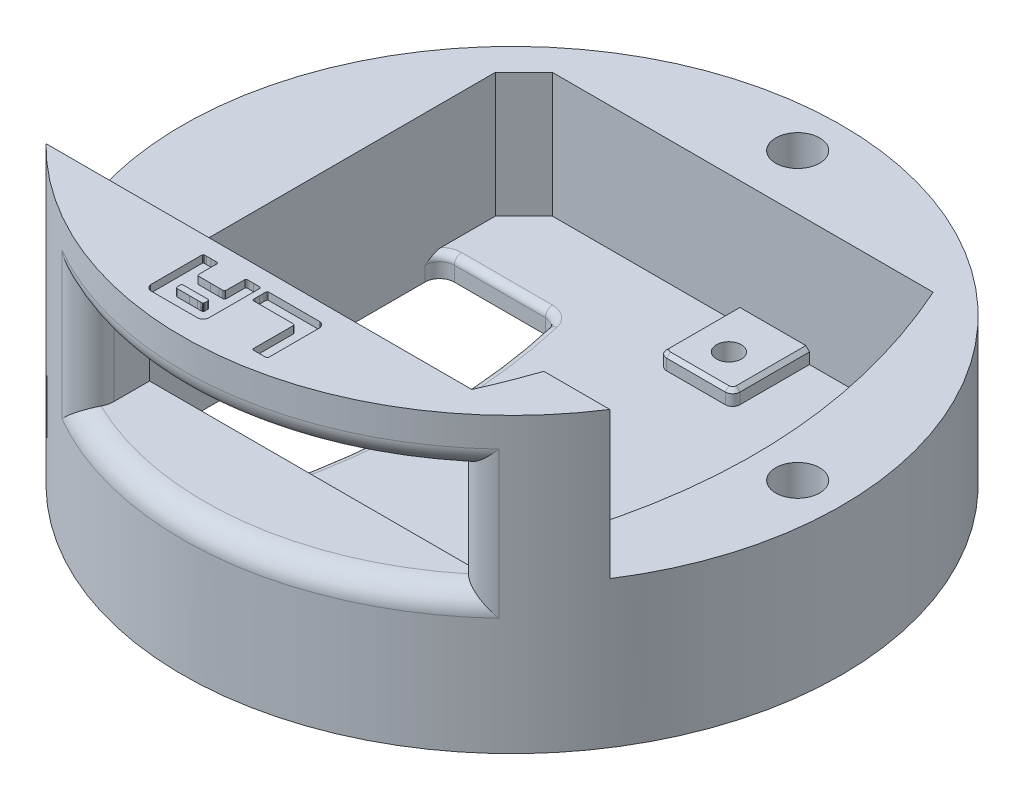
SolidWorks part; units mm, degrees
ref_plane "Plan de face" through (0, 0, 0) normal (0, 0, 1) x (1, 0, 0)
ref_plane "Plan de dessus" through (0, 0, 0) normal (0, 1, 0) x (1, 0, 0)
ref_plane "Plan de droite" through (0, 0, 0) normal (1, 0, 0) x (0, 0, -1)
sketch "Esquisse1" plane through (0, 0, 0) normal (0, 1, 0) x (1, 0, 0)
  circle A0 centre (0, 0) radius 45
  dimension "D1" = 90
extrude "Boss.-Extru.1" add sketch "Esquisse1" along normal blind 40
sketch "Esquisse2" plane through (0, 40, 0) normal (0, 1, 0) x (1, 0, 0)
  line L0 (-26, 31.5) -> (26, 31.5)
  line L1 (26, 0) -> (33, 0) construction
  line L2 (26, 31.5) -> (26, -31.5) construction
  line L3 (-26, 31.5) -> (-29.8891, 27.6109)
  line L4 (-29.8891, 27.6109) -> (-29.8891, 21.6109)
  line L5 (-29.8891, 21.6109) -> (-39.4711, 21.6109)
  line L6 (26, 0) -> (-63.3285, 0) construction
  line L7 (26, 31.5) -> (32.1364, 31.5) construction
  line L8 (-26, 31.5) -> (-32.1364, 31.5) construction
  line L9 (-29.8891, -21.6109) -> (-39.4711, -21.6109)
  line L10 (-29.8891, -27.6109) -> (-29.8891, -21.6109)
  line L11 (-26, -31.5) -> (-29.8891, -27.6109)
  line L12 (-26, -31.5) -> (26, -31.5)
  circle A0 centre (0, 0) radius 45 construction
  arc A1 (-39.4711, -21.6109) -> (-39.4711, 21.6109) centre (0, 0) cw
  spline S0 degree 2 poles (26, 31.5) (40, 0) (26, -31.5) knots 0 0 0 1 1 1
  circle M11 centre (0, 0) radius 45
  dimension "D1" = 52
  dimension "D2" = 7
  dimension "D3" = 63
  dimension "D4" = 135
  dimension "D5" = 5.5
  dimension "D6" = 6
extrude "Enlèv. mat.-Extru.1" cut sketch "Esquisse2" against normal offset from surface (37 mm away) 3 contours S0 L0 L3 L4 L5 L9 L10 L11 L12 M11 region at (-4.3513, 40, 0) up to face at (0, 0, 45)
sketch "Esquisse7" plane through (0, 3, 0) normal (0, 1, 0) x (1, 0, 0)
  line L0 (9.1109, 30) -> (-0.8891, 21) construction
  line L1 (9.1109, 30) -> (9.1109, 22)
  line L2 (8.1109, 21) -> (0.1109, 21)
  line L3 (-0.8891, 30) -> (-0.8891, 22)
  line L4 (-0.8891, 30) -> (9.1109, 30) construction
  line L5 (-0.8891, 30) -> (-0.8891, 31.5)
  line L6 (-0.8891, 31.5) -> (9.1109, 31.5)
  line L7 (9.1109, 30) -> (9.1109, 31.5)
  line L8 (-34.6801, 0) -> (18.839, 0) construction
  line L9 (9.1109, -30) -> (-0.8891, -21) construction
  line L10 (9.1109, -30) -> (9.1109, -31.5)
  line L11 (-0.8891, -31.5) -> (9.1109, -31.5)
  line L12 (-0.8891, -30) -> (-0.8891, -31.5)
  line L13 (-0.8891, -30) -> (-0.8891, -22)
  line L14 (8.1109, -21) -> (0.1109, -21)
  line L15 (9.1109, -30) -> (9.1109, -22)
  line L16 (-34.6801, 21.6109) -> (-34.6801, -21.6109) construction
  line L17 (-26, 31.5) -> (26, 31.5) construction
  line L18 (-29.8891, 21.6109) -> (-39.4711, 21.6109) construction
  arc A0 (0.1109, 21) -> (-0.8891, 22) centre (0.1109, 22) cw
  arc A1 (9.1109, 22) -> (8.1109, 21) centre (8.1109, 22) cw
  arc A2 (9.1109, -22) -> (8.1109, -21) centre (8.1109, -22) ccw
  arc A3 (0.1109, -21) -> (-0.8891, -22) centre (0.1109, -22) ccw
  point P26 (-34.6801, 0)
  point P35 (-34.6801, 21.6109)
  dimension "D2" = 1
  dimension "D1" = 10
  dimension "D3" = 8
  dimension "D4" = 1.5
  dimension "D5" = 33.791
extrude "Boss.-Extru.4" add sketch "Esquisse7" along normal blind 2
chamfer "Chanfrein4" distance 0.5 angle 45 10 edges at (-0.8891, 5, -26.75) (9.1109, 5, -26.75) (-0.5962, 5, -21.2929) (8.818, 5, -21.2929) (4.1109, 5, -21) (9.1109, 5, 26.75) (-0.8891, 5, 26.75) (8.818, 5, 21.2929) (-0.5962, 5, 21.2929) (4.1109, 5, 21)
sketch "Esquisse8" plane through (0, 0, 0) normal (0, -1, 0) x (1, 0, 0)
  line L0 (8.1109, 21.5) -> (0.1109, 21.5) construction
  line L1 (4.1109, 25.5) -> (4.1109, 21.5) construction
  line L2 (0, 0) -> (-4.4948, 0) construction
  circle A0 centre (4.1109, 25.5) radius 1.7
  circle A1 centre (4.1109, -25.5) radius 1.7
  dimension "D1" = 3.4
  dimension "D2" = 4
extrude "Enlèv. mat.-Extru.4" cut sketch "Esquisse8" against normal up to next
chamfer "Chanfrein5" distance 1.5 angle 45 2 edges at (4.1109, 0, -23.8) (4.1109, 0, 23.8)
sketch "Esquisse9" plane through (0, 0, 31.5) normal (0, 0, -1) x (-1, 0, 0)
  line L0 (-26, 33) -> (18, 33)
  line L1 (-26, 33) -> (-26, 19)
  line L2 (-26, 19) -> (18, 19)
  line L3 (18, 33) -> (18, 19)
  line L4 (0.8891, 3) -> (26, 3) construction
  line L5 (-26, 3) -> (-26, 40) construction
  dimension "D1" = 44
  dimension "D2" = 14
  dimension "D3" = 30
extrude "Enlèv. mat.-Extru.5" cut sketch "Esquisse9" against normal up to next
fillet "Congé1" radius 3 4 edges at (26, 26, 36.7287) (4.5929, 33, 44.765) (-18, 26, 41.2432) (4.5929, 19, 44.765)
sketch "Esquisse10" plane through (0, 40, 0) normal (0, 1, 0) x (1, 0, 0)
  line L0 (28.7878, -24.4353) -> (37.7878, -24.4353)
  line L1 (-26, -31.5) -> (-32.1364, -31.5)
  line L2 (-26, -31.5) -> (28.7878, -24.4353)
  arc A0 (-39.4711, -21.6109) -> (-39.4711, 21.6109) centre (0, 0) ccw construction
  arc A1 (-32.1364, -31.5) -> (37.7878, -24.4353) centre (0, 0) cw
  parabola Q5 (26, 31.5) -> (26, -31.5) focus (-2.4375, 0) apex (33, 0) construction
  dimension "D1" = 9
extrude "Enlèv. mat.-Extru.6" cut sketch "Esquisse10" against normal offset from surface (20 mm away) 20 up to face at (4.1109, 0, -22.3)
sketch "Esquisse11" plane through (0, 20, 0) normal (0, 1, 0) x (1, 0, 0)
  line L0 (0, 0) -> (0, 45) construction
  line L1 (0, 0) -> (45, 0) construction
  circle A0 centre (0, 39) radius 1.7
  circle A1 centre (39, 0) radius 1.7
  arc A2 (37.7878, -24.4353) -> (-39.4711, 21.6109) centre (0, 0) ccw construction
  dimension "D1" = 3.4
  dimension "D2" = 3.4
  dimension "D3" = 6
  dimension "D4" = 6
extrude "Enlèv. mat.-Extru.7" cut sketch "Esquisse11" against normal through all
sketch "Esquisse12" plane through (0, 20, 0) normal (0, 1, 0) x (1, 0, 0)
  circle A0 centre (0, 39) radius 3
  circle A1 centre (39, 0) radius 3
  dimension "D1" = 6
  dimension "D2" = 6
extrude "Enlèv. mat.-Extru.8" cut sketch "Esquisse12" against normal blind 10
sketch "Esquisse13" plane through (0, 3, 0) normal (0, 1, 0) x (1, 0, 0)
  line L0 (-29.8891, 21.6109) -> (-29.8891, -21.6109)
  line L1 (-29.8891, -21.6109) -> (-39.4711, -21.6109)
  line L2 (-39.4711, -21.6109) -> (-39.4711, 21.6109) construction
  line L3 (-39.4711, 21.6109) -> (-29.8891, 21.6109)
  arc A0 (-39.4711, 21.6109) -> (-39.4711, -21.6109) centre (0, 0) ccw
extrude "Enlèv. mat.-Extru.9" cut sketch "Esquisse13" against normal up to next
sketch "Esquisse14" plane through (0, 40, 0) normal (0, 1, 0) x (1, 0, 0)
  line L0 (8.3336, -41.5636) -> (8.3347, -40.5342)
  line L1 (8.3343, -38.0353) -> (8.3304, -34.5148)
  line L2 (8.3304, -34.5148) -> (8.3008, -34.4281)
  line L3 (7.7437, -33.8777) -> (7.6504, -33.8481)
  line L4 (7.6504, -33.8481) -> (4.1022, -33.8481)
  line L5 (4.1022, -33.8481) -> (0.5541, -33.8481)
  line L6 (0.5541, -33.8481) -> (0.5063, -33.8845)
  line L7 (0.5227, -35.8917) -> (0.5668, -35.9217)
  line L8 (0.5668, -35.9217) -> (3.3223, -35.9217)
  line L9 (3.3223, -35.9217) -> (6.0778, -35.9217)
  line L10 (6.0778, -35.9217) -> (6.1373, -35.9517)
  line L11 (6.2268, -36.0412) -> (6.2569, -36.1007)
  line L12 (6.2569, -36.1007) -> (6.2569, -38.8562)
  line L13 (6.2569, -38.8562) -> (6.2569, -41.6118)
  line L14 (6.2569, -41.6118) -> (6.2869, -41.6559)
  line L15 (-0.5008, -33.8845) -> (-0.5486, -33.8481)
  line L16 (-0.5486, -33.8481) -> (-1.4297, -33.8443)
  line L17 (-2.4541, -33.9258) -> (-2.4842, -33.9681)
  line L18 (-2.4842, -33.9681) -> (-2.4909, -35.2883)
  line L19 (-2.4909, -35.2883) -> (-2.4976, -36.6084)
  line L20 (-2.4976, -36.6084) -> (-2.5281, -36.6575)
  line L21 (-4.3923, -36.7586) -> (-6.1114, -36.7551)
  line L22 (-6.1114, -36.7551) -> (-6.1563, -36.7231)
  line L23 (-6.2511, -35.2869) -> (-6.2514, -33.992)
  line L24 (-6.2514, -33.992) -> (-6.2814, -33.948)
  line L25 (-8.2975, -33.9399) -> (-8.325, -33.9767)
  line L26 (-8.325, -33.9767) -> (-8.325, -37.5262)
  line L27 (-8.325, -37.5262) -> (-8.325, -41.0756)
  line L28 (-8.325, -41.0756) -> (-8.2954, -41.169)
  line L29 (-7.7449, -41.7261) -> (-7.6582, -41.7557)
  line L30 (-7.6582, -41.7557) -> (-4.4045, -41.7581)
  line L31 (-6.1563, -38.8807) -> (-6.1114, -38.8487)
  line L32 (-6.1114, -38.8487) -> (-4.3923, -38.8452)
  line L33 (-4.3717, -39.6821) -> (-6.0724, -39.6821)
  line L34 (-6.0724, -39.6821) -> (-6.1319, -39.6521)
  arc A0 (8.2111, -41.7438) -> (8.2503, -41.7196) centre (8.1444, -41.5919) ccw
  arc A1 (8.2503, -41.7196) -> (8.2873, -41.6824) centre (8.0739, -41.507) ccw
  arc A2 (8.2873, -41.6824) -> (8.3161, -41.6396) centre (8.08, -41.5119) ccw
  arc A3 (8.3161, -41.6396) -> (8.3304, -41.5987) centre (8.1957, -41.5745) ccw
  arc A4 (8.3304, -41.5987) -> (8.3336, -41.5636) centre (8.1333, -41.5633) ccw
  arc A5 (8.3347, -40.5342) -> (8.3352, -39.3881) centre (-841.87, -39.6126) ccw
  arc A6 (8.3352, -39.3881) -> (8.3343, -38.0353) centre (-1633.4732, -39.822) ccw
  arc A7 (8.3008, -34.4281) -> (8.2131, -34.2445) centre (7.4674, -34.7132) ccw
  arc A8 (8.2131, -34.2445) -> (8.0855, -34.0854) centre (7.4612, -34.7171) ccw
  arc A9 (8.0855, -34.0854) -> (7.9258, -33.9606) centre (7.4691, -34.7091) ccw
  arc A10 (7.9258, -33.9606) -> (7.7437, -33.8777) centre (7.4923, -34.6712) ccw
  arc A11 (0.5063, -33.8845) -> (0.4515, -33.9549) centre (0.6125, -34.0238) ccw
  arc A12 (0.4515, -33.9549) -> (0.426, -34.0571) centre (0.7557, -34.0851) ccw
  arc A13 (0.426, -34.0571) -> (0.4175, -34.2554) centre (2.7542, -34.2551) ccw
  arc A14 (0.4175, -34.2554) -> (0.419, -34.9106) centre (156.8501, -34.2344) ccw
  arc A15 (0.419, -34.9106) -> (0.422, -35.4849) centre (327.504, -33.4972) ccw
  arc A16 (0.422, -35.4849) -> (0.4259, -35.6777) centre (7.164, -35.444) ccw
  arc A17 (0.4259, -35.6777) -> (0.4331, -35.7791) centre (1.8243, -35.6292) ccw
  arc A18 (0.4331, -35.7791) -> (0.4507, -35.824) centre (0.5246, -35.7693) ccw
  arc A19 (0.4507, -35.824) -> (0.4645, -35.8406) centre (0.6004, -35.713) ccw
  arc A20 (0.4645, -35.8406) -> (0.4833, -35.8594) centre (0.774, -35.5501) ccw
  arc A21 (0.4833, -35.8594) -> (0.5038, -35.8774) centre (0.7829, -35.5406) ccw
  arc A22 (0.5038, -35.8774) -> (0.5227, -35.8917) centre (0.6636, -35.6845) ccw
  arc A23 (6.1669, -35.9691) -> (6.1373, -35.9517) centre (6.0187, -36.1869) ccw
  arc A24 (6.1902, -35.9883) -> (6.1669, -35.9691) centre (6.0763, -36.1022) ccw
  arc A25 (6.2095, -36.0117) -> (6.1902, -35.9883) centre (6.0763, -36.1022) ccw
  arc A26 (6.2268, -36.0412) -> (6.2095, -36.0117) centre (5.9916, -36.1598) ccw
  arc A27 (6.2869, -41.6559) -> (6.3011, -41.6748) centre (6.494, -41.5149) ccw
  arc A28 (6.3011, -41.6748) -> (6.3191, -41.6952) centre (6.6379, -41.3956) ccw
  arc A29 (6.3191, -41.6952) -> (6.3379, -41.714) centre (6.6283, -41.4046) ccw
  arc A30 (6.3379, -41.714) -> (6.3545, -41.7278) centre (6.4655, -41.5781) ccw
  arc A31 (6.3545, -41.7278) -> (6.3996, -41.7454) centre (6.4092, -41.654) ccw
  arc A32 (6.3996, -41.7454) -> (6.5022, -41.7525) centre (6.55, -40.319) ccw
  arc A33 (6.5022, -41.7525) -> (6.6973, -41.7562) centre (6.7322, -34.8454) ccw
  arc A34 (6.6973, -41.7562) -> (7.2813, -41.7587) centre (8.4138, 298.5438) ccw
  arc A35 (7.2813, -41.7587) -> (7.7496, -41.7595) centre (7.7994, 113.931) ccw
  arc A36 (7.7496, -41.7595) -> (8.0034, -41.7576) centre (7.7546, -26.229) ccw
  arc A37 (8.0034, -41.7576) -> (8.1674, -41.7537) centre (7.8312, -31.0139) ccw
  arc A38 (8.1674, -41.7537) -> (8.2111, -41.7438) centre (8.1637, -41.636) ccw
  arc A39 (-1.068, -41.7424) -> (-0.9412, -41.7017) centre (-1.217, -41.0597) ccw
  arc A40 (-0.9412, -41.7017) -> (-0.8145, -41.6353) centre (-1.3068, -40.8508) ccw
  arc A41 (-0.8145, -41.6353) -> (-0.698, -41.5491) centre (-1.3195, -40.8305) ccw
  arc A42 (-0.698, -41.5491) -> (-0.6013, -41.4495) centre (-1.2221, -40.9431) ccw
  arc A43 (-0.6013, -41.4495) -> (-0.5559, -41.3871) centre (-1.1275, -41.0203) ccw
  arc A44 (-0.5559, -41.3871) -> (-0.5127, -41.3131) centre (-1.4204, -40.8323) ccw
  arc A45 (-0.5127, -41.3131) -> (-0.474, -41.2323) centre (-1.4999, -40.7902) ccw
  arc A46 (-0.474, -41.2323) -> (-0.4421, -41.149) centre (-1.4788, -40.7993) ccw
  arc A47 (-0.4421, -41.149) -> (-0.4255, -41.0529) centre (-0.7411, -41.0481) ccw
  arc A48 (-0.4255, -41.0529) -> (-0.4202, -40.5962) centre (-62.4465, -40.1056) ccw
  arc A49 (-0.4202, -40.5962) -> (-0.4165, -39.7961) centre (-125.2051, -39.6091) ccw
  arc A50 (-0.4165, -39.7961) -> (-0.4136, -37.5552) centre (-4958.0687, -32.364) ccw
  arc A51 (-0.4136, -37.5552) -> (-0.4116, -34.8688) centre (-4418.828, -32.926) ccw
  arc A52 (-0.4116, -34.8688) -> (-0.4185, -34.2772) centre (-24.8776, -34.8581) ccw
  arc A53 (-0.4185, -34.2772) -> (-0.4388, -33.993) centre (-3.4147, -34.3483) ccw
  arc A54 (-0.4388, -33.993) -> (-0.5008, -33.8845) centre (-0.5981, -34.0121) ccw
  arc A55 (-1.4297, -33.8443) -> (-2.0823, -33.8429) centre (-2.098, -191.4752) ccw
  arc A56 (-2.0823, -33.8429) -> (-2.2852, -33.851) centre (-2.0826, -36.3993) ccw
  arc A57 (-2.2852, -33.851) -> (-2.3884, -33.8747) centre (-2.2564, -34.2128) ccw
  arc A58 (-2.3884, -33.8747) -> (-2.4541, -33.9258) centre (-2.3355, -34.0104) ccw
  arc A59 (-2.5443, -36.6791) -> (-2.5281, -36.6575) centre (-2.6594, -36.5758) ccw
  arc A60 (-2.5661, -36.7006) -> (-2.5443, -36.6791) centre (-2.7327, -36.51) ccw
  arc A61 (-2.5908, -36.7197) -> (-2.5661, -36.7006) centre (-2.739, -36.5028) ccw
  arc A62 (-2.6159, -36.7343) -> (-2.5908, -36.7197) centre (-2.7012, -36.5581) ccw
  arc A63 (-2.687, -36.7523) -> (-2.6159, -36.7343) centre (-2.6954, -36.5701) ccw
  arc A64 (-2.8814, -36.7582) -> (-2.687, -36.7523) centre (-2.9632, -30.7765) ccw
  arc A65 (-3.2474, -36.7604) -> (-2.8814, -36.7582) centre (-3.2177, -12.1526) ccw
  arc A66 (-4.3923, -36.7586) -> (-3.2474, -36.7604) centre (-1.564, 1359.5283) ccw
  arc A67 (-6.1753, -36.7069) -> (-6.1563, -36.7231) centre (-6.0726, -36.6058) ccw
  arc A68 (-6.1952, -36.6844) -> (-6.1753, -36.7069) centre (-5.9615, -36.4964) ccw
  arc A69 (-6.2132, -36.6597) -> (-6.1952, -36.6844) centre (-5.9561, -36.492) ccw
  arc A70 (-6.226, -36.6364) -> (-6.2132, -36.6597) centre (-6.0662, -36.5639) ccw
  arc A71 (-6.2414, -36.5728) -> (-6.226, -36.6364) centre (-6.0662, -36.5639) ccw
  arc A72 (-6.2473, -36.4048) -> (-6.2414, -36.5728) centre (-1.0597, -36.3083) ccw
  arc A73 (-6.2504, -36.1005) -> (-6.2473, -36.4048) centre (11.5933, -36.0728) ccw
  arc A74 (-6.2511, -35.2869) -> (-6.2504, -36.1005) centre (606.421, -35.1486) ccw
  arc A75 (-6.2814, -33.948) -> (-6.2956, -33.929) centre (-6.4884, -34.0888) ccw
  arc A76 (-6.2956, -33.929) -> (-6.3136, -33.9086) centre (-6.6323, -34.2081) ccw
  arc A77 (-6.3136, -33.9086) -> (-6.3324, -33.8898) centre (-6.6228, -34.1992) ccw
  arc A78 (-6.3324, -33.8898) -> (-6.349, -33.876) centre (-6.46, -34.0257) ccw
  arc A79 (-6.349, -33.876) -> (-6.3943, -33.8584) centre (-6.4036, -33.9496) ccw
  arc A80 (-6.3943, -33.8584) -> (-6.4978, -33.8517) centre (-6.5407, -35.2993) ccw
  arc A81 (-6.4978, -33.8517) -> (-6.695, -33.8486) centre (-6.7067, -40.9083) ccw
  arc A82 (-6.695, -33.8486) -> (-7.2915, -33.8481) centre (-7.2912, -393.2007) ccw
  arc A83 (-7.2915, -33.8481) -> (-7.8847, -33.8486) centre (-7.2913, -386.0898) ccw
  arc A84 (-7.8847, -33.8486) -> (-8.0836, -33.8516) centre (-7.8725, -41.0822) ccw
  arc A85 (-8.0836, -33.8516) -> (-8.1885, -33.8583) centre (-8.0385, -35.3954) ccw
  arc A86 (-8.1885, -33.8583) -> (-8.2332, -33.8756) centre (-8.1799, -33.947) ccw
  arc A87 (-8.2332, -33.8756) -> (-8.2493, -33.8888) centre (-8.0952, -34.0603) ccw
  arc A88 (-8.2493, -33.8888) -> (-8.2672, -33.9058) centre (-7.9414, -34.2316) ccw
  arc A89 (-8.2672, -33.9058) -> (-8.2843, -33.9238) centre (-7.9414, -34.2316) ccw
  arc A90 (-8.2843, -33.9238) -> (-8.2975, -33.9399) centre (-8.1127, -34.0778) ccw
  arc A91 (-8.2954, -41.169) -> (-8.2124, -41.3515) centre (-7.4953, -40.9155) ccw
  arc A92 (-8.2124, -41.3515) -> (-8.0879, -41.511) centre (-7.4692, -40.8996) ccw
  arc A93 (-8.0879, -41.511) -> (-7.929, -41.6383) centre (-7.4611, -40.8916) ccw
  arc A94 (-7.929, -41.6383) -> (-7.7449, -41.7261) centre (-7.4574, -40.8858) ccw
  arc A95 (-4.4045, -41.7581) -> (-2.6497, -41.7587) centre (-2.7092, 2304.2614) ccw
  arc A96 (-2.6497, -41.7587) -> (-1.7515, -41.7566) centre (-2.6547, 149.9899) ccw
  arc A97 (-1.7515, -41.7566) -> (-1.1629, -41.753) centre (-2.7432, 168.7567) ccw
  arc A98 (-1.1629, -41.753) -> (-1.068, -41.7424) centre (-1.1664, -41.2915) ccw
  arc A99 (-6.1614, -39.6348) -> (-6.1319, -39.6521) centre (-6.0133, -39.4169) ccw
  arc A100 (-6.1847, -39.6155) -> (-6.1614, -39.6348) centre (-6.0709, -39.5016) ccw
  arc A101 (-6.204, -39.5922) -> (-6.1847, -39.6155) centre (-6.0709, -39.5016) ccw
  arc A102 (-6.2214, -39.5626) -> (-6.204, -39.5922) centre (-5.9862, -39.444) ccw
  arc A103 (-6.2381, -39.5202) -> (-6.2214, -39.5626) centre (-5.9976, -39.4498) ccw
  arc A104 (-6.2468, -39.4756) -> (-6.2381, -39.5202) centre (-6.0036, -39.4515) ccw
  arc A105 (-6.2504, -39.4082) -> (-6.2468, -39.4756) centre (-5.4887, -39.4006) ccw
  arc A106 (-6.2511, -39.2626) -> (-6.2504, -39.4082) centre (6.6941, -39.2784) ccw
  arc A107 (-6.2476, -39.0858) -> (-6.2511, -39.2626) centre (-1.5054, -39.2684) ccw
  arc A108 (-6.2342, -38.9915) -> (-6.2476, -39.0858) centre (-5.7823, -39.1037) ccw
  arc A109 (-6.206, -38.9304) -> (-6.2342, -38.9915) centre (-6.0604, -39.0346) ccw
  arc A110 (-6.1563, -38.8807) -> (-6.206, -38.9304) centre (-6.032, -39.055) ccw
  arc A111 (-3.2474, -38.8434) -> (-4.3923, -38.8452) centre (-1.564, -1435.1321) ccw
  arc A112 (-2.8814, -38.8456) -> (-3.2474, -38.8434) centre (-3.2177, -63.4512) ccw
  arc A113 (-2.687, -38.8515) -> (-2.8814, -38.8456) centre (-2.9632, -44.8273) ccw
  arc A114 (-2.6159, -38.8695) -> (-2.687, -38.8515) centre (-2.6954, -39.0337) ccw
  arc A115 (-2.5908, -38.8841) -> (-2.6159, -38.8695) centre (-2.7012, -39.0457) ccw
  arc A116 (-2.5661, -38.9032) -> (-2.5908, -38.8841) centre (-2.739, -39.101) ccw
  arc A117 (-2.5443, -38.9247) -> (-2.5661, -38.9032) centre (-2.7327, -39.0938) ccw
  arc A118 (-2.5281, -38.9463) -> (-2.5443, -38.9247) centre (-2.6594, -39.028) ccw
  arc A119 (-2.5107, -38.9839) -> (-2.5281, -38.9463) centre (-2.6722, -39.0359) ccw
  arc A120 (-2.5019, -39.0263) -> (-2.5107, -38.9839) centre (-2.7022, -39.0456) ccw
  arc A121 (-2.4983, -39.0952) -> (-2.5019, -39.0263) centre (-3.2845, -39.1019) ccw
  arc A122 (-2.4976, -39.2621) -> (-2.4983, -39.0952) centre (-22.0355, -39.2621) ccw
  arc A123 (-2.4983, -39.4287) -> (-2.4976, -39.2621) centre (-21.9238, -39.2621) ccw
  arc A124 (-2.5019, -39.4977) -> (-2.4983, -39.4287) centre (-3.2907, -39.4219) ccw
  arc A125 (-2.5106, -39.5401) -> (-2.5019, -39.4977) centre (-2.7041, -39.4783) ccw
  arc A126 (-2.5279, -39.5776) -> (-2.5106, -39.5401) centre (-2.6701, -39.4892) ccw
  arc A127 (-2.5438, -39.5987) -> (-2.5279, -39.5776) centre (-2.6545, -39.4988) ccw
  arc A128 (-2.5657, -39.6204) -> (-2.5438, -39.5987) centre (-2.7467, -39.4157) ccw
  arc A129 (-2.5903, -39.6398) -> (-2.5657, -39.6204) centre (-2.7521, -39.4096) ccw
  arc A130 (-2.6146, -39.6542) -> (-2.5903, -39.6398) centre (-2.6965, -39.4887) ccw
  arc A131 (-2.6846, -39.6724) -> (-2.6146, -39.6542) centre (-2.6932, -39.4954) ccw
  arc A132 (-2.8772, -39.6786) -> (-2.6846, -39.6724) centre (-2.9707, -33.7894) ccw
  arc A133 (-3.2396, -39.6816) -> (-2.8772, -39.6786) centre (-3.2599, -15.5832) ccw
  arc A134 (-4.3717, -39.6821) -> (-3.2396, -39.6816) centre (-4.3808, 1320.9145) ccw
extrude "Signature" cut sketch "Esquisse14" against normal blind 1
sketch "Esquisse15" plane through (0, 20, 0) normal (0, 1, 0) x (1, 0, 0)
  line L0 (-39.4711, 21.6109) -> (-29.8891, 21.6109)
  line L1 (-29.8891, 21.6109) -> (-29.8891, -21.6109)
  line L2 (-29.8891, -21.6109) -> (-39.4711, -21.6109)
  arc A0 (-39.4711, -21.6109) -> (-39.4711, 21.6109) centre (0, 0) cw
extrude "Boss.-Extru.5" add sketch "Esquisse15" against normal up to surface (20 mm away) up to face at (0, 0, -37.3)
sketch "Esquisse16" plane through (0, 3, 0) normal (0, 1, 0) x (1, 0, 0)
  line L0 (-29.8891, 20) -> (-13.8891, 20)
  line L1 (-29.8891, -27.6109) -> (-29.8891, 27.6109) construction
  line L2 (-13.8891, 20) -> (-13.8891, -20) construction
  line L3 (-13.8891, -20) -> (-29.8891, -20)
  line L4 (-29.8891, -20) -> (-29.8891, 20)
  line L5 (0, 0) -> (-13.8891, 0) construction
  arc A0 (-13.8891, 20) -> (-13.8891, -20) centre (-93.4127, 0) cw
  dimension "D1" = 16
  dimension "D2" = 82
  dimension "D3" = 40
extrude "Enlèv. mat.-Extru.10" cut sketch "Esquisse16" against normal up to next
fillet "Congé2" radius 2 4 edges at (-13.8891, 1.5, 20) (-29.8891, 1.5, 20) (-29.8891, 1.5, -20) (-13.8891, 1.5, -20)
fillet "Congé3" radius 1 7 edges at (-29.3033, 3, 19.4142) (-21.6765, 3, 20) (-14.219, 3, 19.5652) (-29.3033, 3, -19.4142) (-21.6765, 3, -20) (-14.219, 3, -19.5652) (-11.4127, 3, 0)
sketch "Esquisse17" plane through (0, 0, 0) normal (0, -1, 0) x (1, 0, 0)
  line L0 (-29.8891, 18) -> (-29.8891, -18) construction
  line L1 (-29.8891, 3.5) -> (-51.7101, 3.5)
  line L2 (-29.8891, 3.5) -> (-29.8891, -3.5)
  line L3 (-29.8891, -3.5) -> (-51.7101, -3.5)
  line L4 (-51.7101, 3.5) -> (-51.7101, -3.5)
  line L5 (-29.8891, 0) -> (0, 0) construction
  dimension "D1" = 7
extrude "Enlèv. mat.-Extru.11" cut sketch "Esquisse17" against normal blind 3
fillet "Congé4" radius 1 8 edges at (-29.8891, 1.5, 3.5) (-44.8637, 1.5, -3.5) (-29.8891, 3, 0) (-45, 3, 0) (-29.8891, 1.5, -3.5) (-44.8637, 1.5, 3.5) (-37.3764, 3, 3.5) (-37.3764, 3, -3.5)
